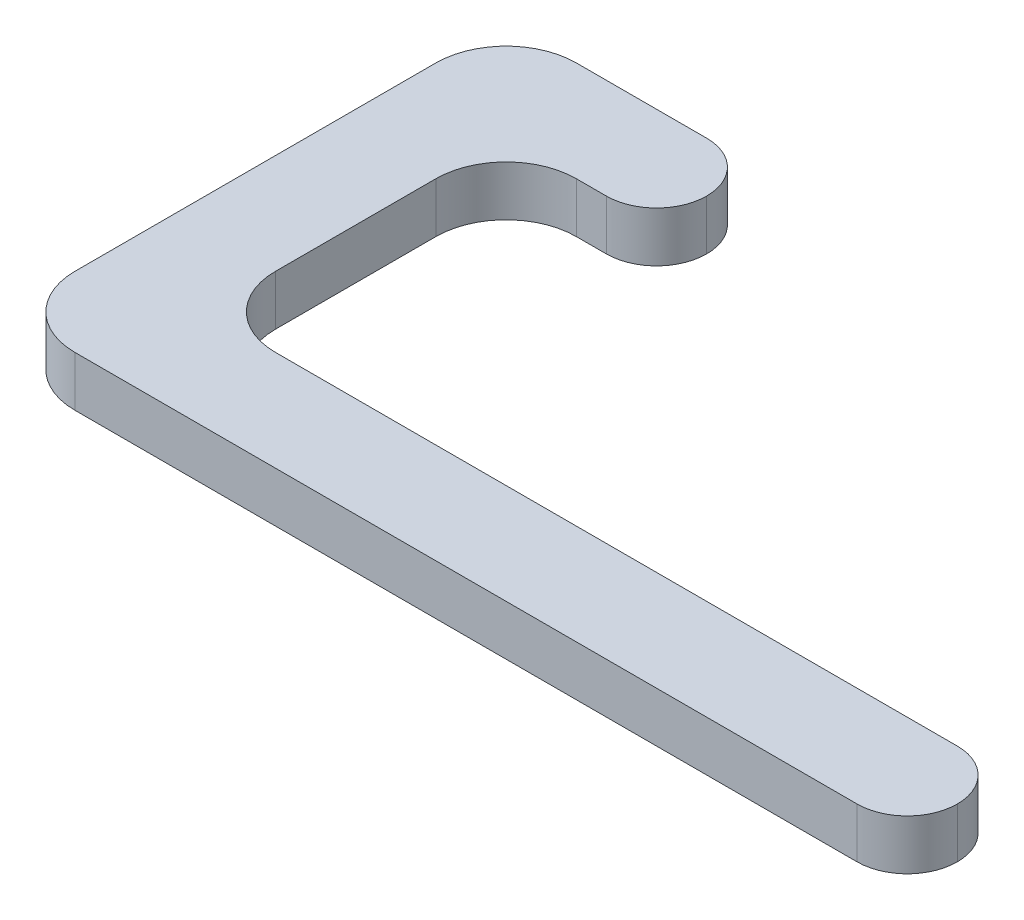
SolidWorks part; units mm, degrees
ref_plane "Front Plane" through (0, 0, 0) normal (0, 0, 1) x (1, 0, 0)
ref_plane "Top Plane" through (0, 0, 0) normal (0, 1, 0) x (1, 0, 0)
ref_plane "Right Plane" through (0, 0, 0) normal (1, 0, 0) x (0, 0, -1)
sketch "Sketch1" plane through (0, 0, 0) normal (0, 1, 0) x (1, 0, 0)
  line L0 (0, 0) -> (0, 15)
  line L1 (0, 15) -> (7.5, 15)
  line L2 (0, 0) -> (40, 0)
  point P3 (40, 0)
  point P5 (0, 14.4667)
  point P7 (7.6, 14.2)
  dimension "D1" = 40
  dimension "D2" = 15
  dimension "D3" = 7.5
extrude "Extrude-Thin1" add sketch "Sketch1" along normal blind 2.5 thin thin type one direction wall 5
fillet "Fillet1" radius 2.5 4 edges at (40, 1.25, 5) (40, 1.25, 0) (7.5, 1.25, -15) (7.5, 1.25, -20)
fillet "Fillet2" radius 3.5 4 edges at (0, 1.25, 0) (-5, 1.25, 5) (-5, 1.25, -20) (0, 1.25, -15)
